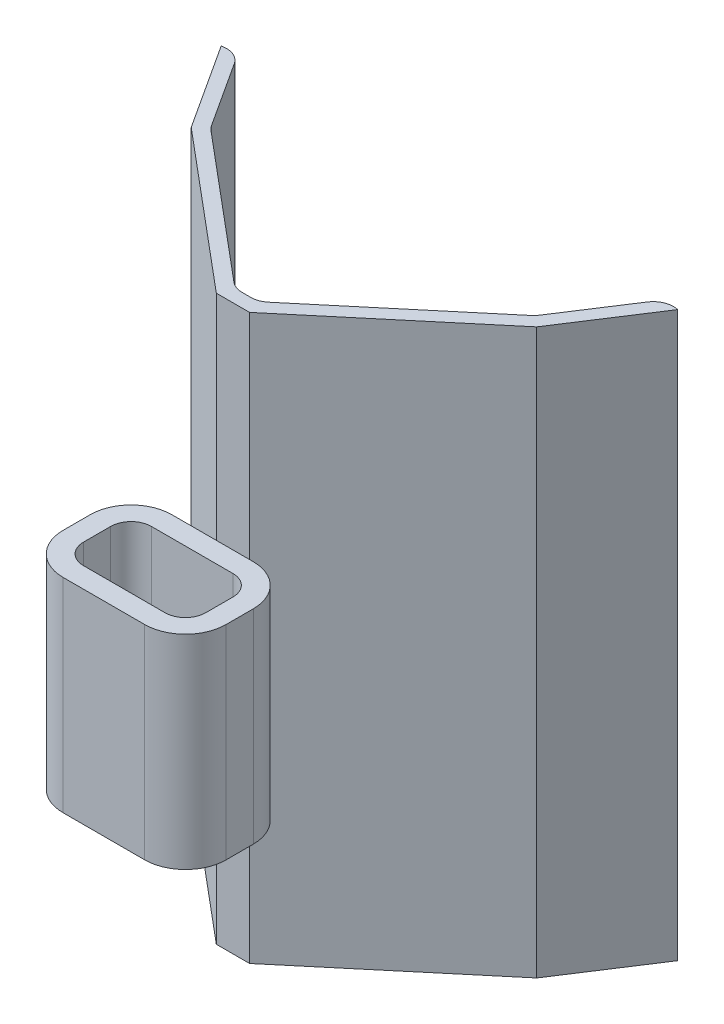
SolidWorks part; units mm, degrees
ref_plane "Alzado" through (0, 0, 0) normal (0, 0, 1) x (1, 0, 0)
ref_plane "Planta" through (0, 0, 0) normal (0, 1, 0) x (1, 0, 0)
ref_plane "Vista lateral" through (0, 0, 0) normal (1, 0, 0) x (0, 0, -1)
sketch "Croquis1" plane through (0, 0, 0) normal (0, 1, 0) x (1, 0, 0)
  line L0 (-6, 8) -> (6, 8)
  line L1 (-6, -5) -> (6, -5)
  line L2 (-9, -2) -> (-9, 2)
  line L3 (-6, 5) -> (6, 5)
  line L4 (9, -2) -> (9, 2)
  line L5 (-9, -5) -> (9, 5) construction
  line L6 (-9, 5) -> (9, -5) construction
  line L7 (12, -2) -> (12, 2)
  line L8 (-6, -8) -> (6, -8)
  line L9 (-12, -2) -> (-12, 2)
  arc A0 (6, 5) -> (9, 2) centre (6, 2) cw
  arc A1 (6, -5) -> (9, -2) centre (6, -2) ccw
  arc A2 (-6, -5) -> (-9, -2) centre (-6, -2) cw
  arc A3 (-9, 2) -> (-6, 5) centre (-6, 2) cw
  arc A4 (6, 8) -> (12, 2) centre (6, 2) cw
  arc A5 (6, -8) -> (12, -2) centre (6, -2) ccw
  arc A6 (-6, -8) -> (-12, -2) centre (-6, -2) cw
  arc A7 (-12, 2) -> (-6, 8) centre (-6, 2) cw
  point P0 (0, 0)
  dimension "D3" = 3
  dimension "D1" = 10
  dimension "D2" = 18
  dimension "D4" = 3
extrude "Saliente-Extruir1" add sketch "Croquis1" along normal blind 30
sketch "Croquis3" plane through (0, 0, -8) normal (0, 0, -1) x (-1, 0, 0)
  line L0 (0, 15) -> (0, 0) construction
  line L1 (-2.4468, 12.9911) -> (2.4468, 12.9911)
  line L2 (-2.4468, 12.9911) -> (-2.4468, 17.0089)
  line L3 (-2.4468, 17.0089) -> (2.4468, 17.0089)
  line L4 (2.4468, 12.9911) -> (2.4468, 17.0089)
  line L5 (-2.4468, 12.9911) -> (2.4468, 17.0089) construction
  line L6 (-2.4468, 17.0089) -> (2.4468, 12.9911) construction
  point P0 (0, 15)
extrude "Saliente-Extruir2" add sketch "Croquis3" along normal blind 3
sketch "Croquis7" plane through (0, 17.0089, 0) normal (0, 1, 0) x (1, 0, 0)
  line L0 (0, 11) -> (0, 15.2379) construction
  line L1 (-2.4468, 11) -> (2.4468, 11) construction
  line L2 (-2.4468, 11) -> (2.4468, 11)
  line L9 (-2.4468, 11) -> (-25.4281, 30.2836)
  line L10 (2.4468, 11) -> (25.4281, 30.2836)
  line L11 (-25.4281, 30.2836) -> (-33.5977, 42.8637)
  line L12 (25.4281, 30.2836) -> (33.5977, 42.8637)
  line L13 (23.9135, 31.6236) -> (31.9203, 43.953)
  line L14 (1.7188, 13) -> (23.9135, 31.6236)
  line L15 (-1.7188, 13) -> (1.7188, 13)
  line L16 (-1.7188, 13) -> (-23.9135, 31.6236)
  line L17 (-23.9135, 31.6236) -> (-31.9203, 43.953)
  line L18 (-33.5977, 42.8637) -> (-31.9203, 43.953)
  line L19 (31.9203, 43.953) -> (33.5977, 42.8637)
  dimension "D1" = 140
  dimension "D2" = 30
  dimension "D3" = 163
  dimension "D4" = 15
  dimension "D5" = 2
extrude "Saliente-Extruir3" add sketch "Croquis7" along normal mid plane 83
fillet "Redondeo2" radius 3 6 edges at (31.9203, 17.0089, -43.953) (-31.9203, 17.0089, -43.953) (-23.9135, 17.0089, -31.6236) (23.9135, 17.0089, -31.6236) (1.7188, 17.0089, -13) (-1.7188, 17.0089, -13)
